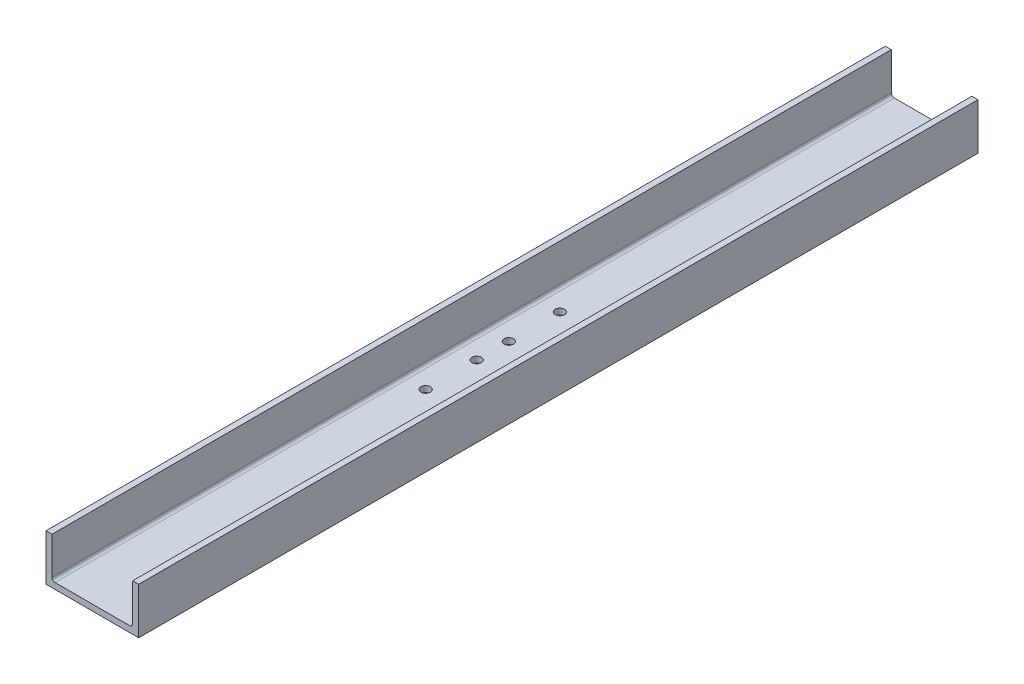
SolidWorks part; units mm, degrees
ref_plane "Front Plane" through (0, 0, 0) normal (0, 0, 1) x (1, 0, 0)
ref_plane "Top Plane" through (0, 0, 0) normal (0, 1, 0) x (1, 0, 0)
ref_plane "Right Plane" through (0, 0, 0) normal (1, 0, 0) x (0, 0, -1)
sketch "Sketch1" plane through (0, 0, 0) normal (0, 0, 1) x (1, 0, 0)
  line L0 (-25.4, 12.7) -> (-25.4, -12.7) construction
  line L1 (-25.4, -12.7) -> (25.4, -12.7) construction
  line L2 (25.4, -12.7) -> (25.4, 12.7) construction
  line L3 (22.098, -9.398) -> (-22.098, -9.398) construction
  line L4 (-22.098, -9.398) -> (-22.098, 12.7) construction
  line L6 (-22.098, 12.7) -> (-25.4, 12.7) construction
  line L7 (0, -12.7) -> (0, 0) construction
  line L8 (25.4, 12.7) -> (22.098, 12.7) construction
  line L9 (22.098, 12.7) -> (22.098, -9.398) construction
  line L10 (0, -9.398) -> (0, -12.7) construction
  point P4 (0, 0)
  point P11 (25.4, -9.398)
  dimension "Outside Height" = 25.4
  dimension "Outside Width" = 50.8
  dimension "Leg Thickness" = 3.302
  dimension "D1" = 12.7
  dimension "Inside Height" = 22.098
  dimension "Inside Width" = 44.196
  dimension "Base Thickness" = 3.302
sketch "Sketch2" plane through (0, 0, 0) normal (1, 0, 0) x (0, 0, -1)
  line L0 (230, 12.7) -> (-230, 12.7) construction
  line L1 (0, -9.398) -> (0, 12.7) construction
  point P0 (-179.2, 12.7)
  point P4 (0, 12.7)
  point P6 (179.2, 12.7)
  dimension "D1" = 50.8
  dimension "D2" = 50.8
  dimension "Length" = 460
sketch "Sketch3" plane through (0, 0, 0) normal (0, 0, 1) x (1, 0, 0)
  line L6 (-25.4, 12.7) -> (-25.4, -12.7)
  line L7 (-25.4, -12.7) -> (25.4, -12.7)
  line L8 (25.4, -12.7) -> (25.4, 12.7)
  line L9 (25.4, 12.7) -> (22.098, 12.7)
  line L10 (22.098, 12.7) -> (22.098, -9.398)
  line L11 (22.098, -9.398) -> (-22.098, -9.398)
  line L12 (-22.098, -9.398) -> (-22.098, 12.7)
  line L13 (-22.098, 12.7) -> (-25.4, 12.7)
extrude "Boss-Extrude1" add sketch "Sketch3" along normal mid plane 460
fillet "Fillet1" radius 1.651 2 edges at (22.098, -9.398, 0) (-22.098, -9.398, 0)
sketch "Sketch4" plane through (0, -9.398, 0) normal (0, 1, 0) x (1, 0, 0)
  line L0 (0, 230) -> (0, -230) construction
  line L1 (20.447, 230) -> (-20.447, 230) construction
  line L2 (20.447, -230) -> (-20.447, -230) construction
  line L3 (-23.5304, 0) -> (23.5304, 0) construction
  circle A0 centre (-10.5304, 8.79) radius 2.585
  circle A1 centre (10.4696, 8.79) radius 2.585
  circle A2 centre (-10.5304, 36.79) radius 2.585
  circle A3 centre (10.4696, 36.79) radius 2.585
  circle A4 centre (-10.5304, -36.79) radius 2.585
  circle A5 centre (10.4696, -36.79) radius 2.585
  circle A6 centre (10.4696, -8.79) radius 2.585
  circle A7 centre (-10.5304, -8.79) radius 2.585
  point P24 (0, 0)
  point P26 (0, 0)
  dimension "D1" = 5.17
  dimension "D2" = 5.17
  dimension "D3" = 28
  dimension "D4" = 8.79
  dimension "D5" = 8.79
  dimension "D6" = 28
extrude "Cut-Extrude1" cut sketch "Sketch4" against normal blind 10
equation "\"D1@Boss-Extrude1\"=\"Length@Sketch2\""
equation "\"D2@Sketch2\"=\"D1@Sketch2\""
equation "\"D1@Sketch1\"=\"Outside Height@Sketch1\"/2"
equation "\"D1@Fillet1\"=\"Leg Thickness@Sketch1\"*.5"
equation "\"D1@Sketch2\"=\"Outside Width@Sketch1\"*1"
